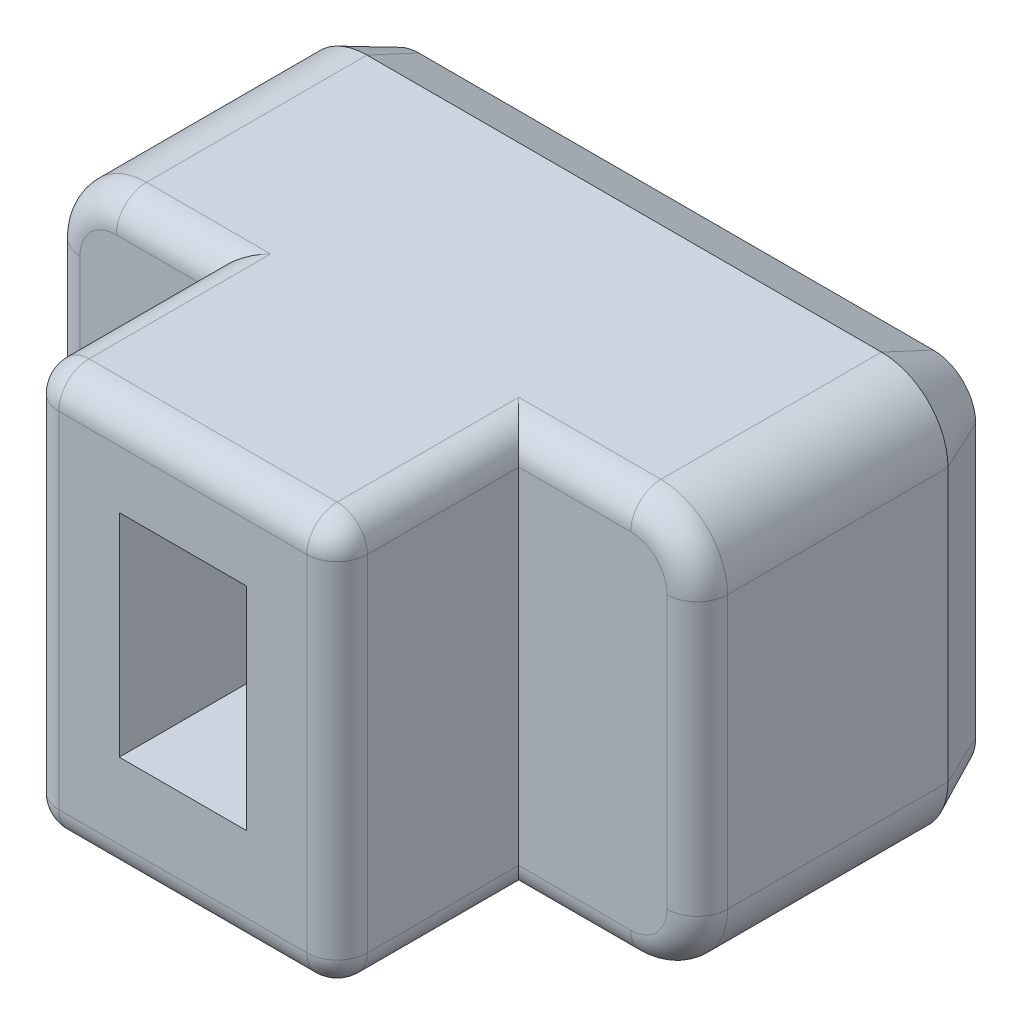
SolidWorks part; units mm, degrees
ref_plane "Plan de face" through (0, 0, 0) normal (0, 0, 1) x (1, 0, 0)
ref_plane "Plan de dessus" through (0, 0, 0) normal (0, 1, 0) x (1, 0, 0)
ref_plane "Plan de droite" through (0, 0, 0) normal (1, 0, 0) x (0, 0, -1)
sketch "Esquisse2" plane through (0, 0, 0) normal (0, 0, 1) x (1, 0, 0)
  line L1 (1.1, 0) -> (9.6, 0)
  line L2 (0, 1.1) -> (0, 5.6)
  line L3 (1.1, 6.7) -> (9.6, 6.7)
  line L4 (10.7, 1.1) -> (10.7, 5.6)
  arc A0 (9.6, 6.7) -> (10.7, 5.6) centre (9.6, 5.6) cw
  arc A1 (9.6, 0) -> (10.7, 1.1) centre (9.6, 1.1) ccw
  arc A2 (1.1, 0) -> (0, 1.1) centre (1.1, 1.1) cw
  arc A3 (0, 5.6) -> (1.1, 6.7) centre (1.1, 5.6) cw
  point P7 (10.7, 6.7)
  point P12 (0, 0)
  point P15 (0, 6.7)
  dimension "D3" = 1.1
  dimension "D1" = 10.7
  dimension "D2" = 6.7
extrude "Boss.-Extru.1" add sketch "Esquisse2" along normal blind 8
sketch "Esquisse3" plane through (0, 0, 8) normal (0, 0, 1) x (1, 0, 0)
  line L0 (0, 5.6) -> (0, 1.1) construction
  line L1 (4.15, 5.25) -> (6.25, 5.25)
  line L2 (4.15, 5.25) -> (4.15, 1.75)
  line L3 (4.15, 1.75) -> (6.25, 1.75)
  line L4 (6.25, 5.25) -> (6.25, 1.75)
  line L5 (10.7, 1.1) -> (10.7, 5.6) construction
  line L6 (9.6, 6.7) -> (1.1, 6.7) construction
  line L7 (1.1, 0) -> (9.6, 0) construction
  dimension "D1" = 2.1
  dimension "D2" = 3.5
  dimension "D3" = 4.15
  dimension "D4" = 4.45
  dimension "D5" = 1.45
  dimension "D6" = 1.75
extrude "Enlèv. mat.-Extru.1" cut sketch "Esquisse3" against normal blind 3
sketch "Esquisse4" plane through (0, 0, 8) normal (0, 0, 1) x (1, 0, 0)
  line L0 (2.65, 6.7) -> (2.65, 0)
  line L1 (9.6, 6.7) -> (1.1, 6.7) construction
  line L2 (1.1, 0) -> (9.6, 0) construction
  line L3 (2.65, 0) -> (7.75, 0)
  line L4 (7.75, 0) -> (7.75, 6.7)
  line L5 (7.75, 6.7) -> (2.65, 6.7)
  line L6 (4.15, 5.25) -> (4.15, 1.75) construction
  line L7 (6.25, 1.75) -> (6.25, 5.25) construction
  dimension "D1" = 1.5
  dimension "D2" = 1.5
extrude "Enlèv. mat.-Extru.2" cut sketch "Esquisse4" against normal blind 3 flip side to cut
fillet "Congé1" radius 0.5 18 edges at (8.675, 0, 5) (10.3778, 0.3222, 5) (10.7, 3.35, 5) (10.3778, 6.3778, 5) (1.875, 6.7, 5) (0.3222, 6.3778, 5) (1.875, 0, 5) (0.3222, 0.3222, 5) (7.75, 6.7, 6.5) (2.65, 6.7, 6.5) (7.75, 0, 6.5) (2.65, 0, 6.5) (2.65, 3.35, 8) (5.2, 6.7, 8) (7.75, 3.35, 8) (5.2, 0, 8) (8.675, 6.7, 5) (0, 3.35, 5)
chamfer "Chanfrein1" distance 0.4 angle 65 8 edges at (5.35, 0, 0) (10.3778, 0.3222, 0) (0.3222, 0.3222, 0) (10.7, 3.35, 0) (0, 3.35, 0) (10.3778, 6.3778, 0) (0.3222, 6.3778, 0) (5.35, 6.7, 0) first distance on face at (5.35, 3.35, 0)
sketch "Esquisse5" plane through (0, 0, 0) normal (0, 0, 1) x (1, 0, 0)
  line L0 (-0.9378, 5.093) -> (11.6517, 5.093) construction
  text T0 "OBS" font "Corbel" height 3.5
extrude "Enlèv. mat.-Extru.3" cut sketch "Esquisse5" along normal blind 0.2
extrude "Boss.-Extru.2" add sketch "Esquisse5<4>" against normal blind 0.2
sketch "Esquisse5<4>" plane through (0, 0, 0) normal (0, 0, 1) x (1, 0, 0) same geometry as "Esquisse5"
